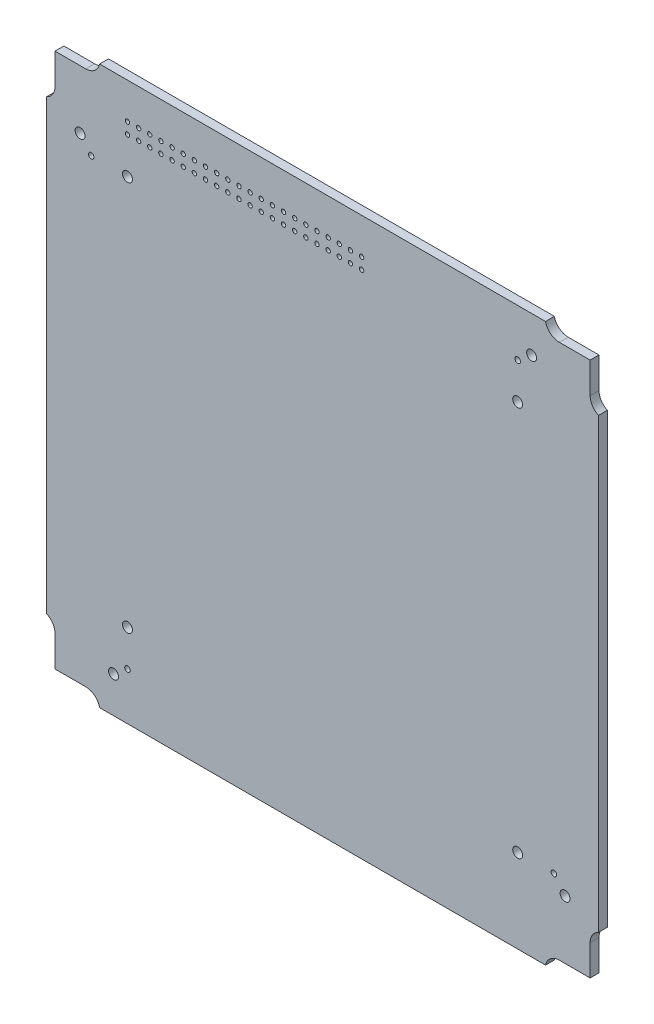
SolidWorks part; units mm, degrees
ref_plane "Front Plane" through (0, 0, 0) normal (0, 0, 1) x (1, 0, 0)
ref_plane "Top Plane" through (0, 0, 0) normal (0, 1, 0) x (1, 0, 0)
ref_plane "Right Plane" through (0, 0, 0) normal (1, 0, 0) x (0, 0, -1)
sketch "Sketch1" plane through (0, 0, 0) normal (0, 0, 1) x (1, 0, 0)
  line L0 (-40, 50) -> (-40, 48)
  line L1 (-50, -50) -> (50, -50)
  line L2 (-50, -50) -> (-50, 50)
  line L3 (-50, 50) -> (50, 50)
  line L4 (50, -50) -> (50, 50)
  line L5 (-50, -50) -> (50, 50) construction
  line L6 (-50, 50) -> (50, -50) construction
  line L7 (-50, 50) -> (-40, 50)
  line L8 (-50, 50) -> (-50, 40)
  line L9 (-40, 48) -> (-48, 48)
  line L10 (-48, 48) -> (-48, 40)
  line L11 (50, 50) -> (40, 50)
  line L12 (50, 50) -> (50, 40)
  line L13 (-48, 40) -> (-50, 40)
  line L14 (50, 40) -> (48, 40)
  line L15 (-50, -50) -> (-37.8649, -50)
  line L16 (-50, -50) -> (-50, -37.8649)
  line L17 (50, 50) -> (50, 40)
  line L18 (50, 50) -> (40, 50)
  line L19 (50, -50) -> (41.5, -50)
  line L20 (50, -50) -> (50, -41.5)
  line L21 (48, 40) -> (48, 48)
  line L22 (48, 48) -> (40, 48)
  line L23 (40, 48) -> (40, 50)
  line L24 (40, -50) -> (40, -48)
  line L25 (50, -50) -> (40, -50)
  line L26 (50, -50) -> (50, -40)
  line L27 (40, -48) -> (48, -48)
  line L28 (48, -48) -> (48, -40)
  line L29 (48, -40) -> (50, -40)
  line L30 (-50, -40) -> (-48, -40)
  line L31 (-50, -50) -> (-50, -40)
  line L32 (-50, -50) -> (-40, -50)
  line L33 (-48, -40) -> (-48, -48)
  line L34 (-48, -48) -> (-40, -48)
  line L35 (-40, -48) -> (-40, -50)
  point P0 (0, 0)
  point P38 (0, 0)
  dimension "D1" = 100
  dimension "D2" = 100
  dimension "D3" = 2
  dimension "D4" = 10
  dimension "D5" = 4
extrude "Boss-Extrude1" add sketch "Sketch1" along normal blind 1.5875 contours L1 L4 L3 L2 region at (0, 0, 0)
fillet "Fillet1" radius 2.54 8 edges at (-48, -40, 0.7937) (-40, -48, 0.7937) (40, -48, 0.7937) (48, -40, 0.7937) (48, 40, 0.7937) (40, 48, 0.7937) (-40, 48, 0.7937) (-48, 40, 0.7937)
sketch "Sketch5" plane through (0, 0, 1.5875) normal (0, 0, 1) x (1, 0, 0)
  line L0 (0, 50) -> (0, -50) construction
  line L5 (-40, 50) -> (40, 50) construction
  line L6 (-40, -50) -> (40, -50) construction
  line L8 (-35.7478, 50) -> (8.2522, 50) construction
  line L9 (-35.7478, 50) -> (-35.7478, 45.8) construction
  line L10 (-35.7478, 45.8) -> (8.2522, 45.8) construction
  line L11 (8.2522, 50) -> (8.2522, 45.8) construction
  circle A0 centre (-35, 43.55) radius 0.395
  circle A1 centre (-33, 43.55) radius 0.395
  circle A2 centre (-31, 43.55) radius 0.395
  circle A3 centre (-29, 43.55) radius 0.395
  circle A4 centre (-27, 43.55) radius 0.395
  circle A5 centre (-25, 43.55) radius 0.395
  circle A6 centre (-23, 43.55) radius 0.395
  circle A7 centre (-21, 43.55) radius 0.395
  circle A8 centre (-19, 43.55) radius 0.395
  circle A9 centre (-17, 43.55) radius 0.395
  circle A10 centre (-15, 43.55) radius 0.395
  circle A11 centre (-13, 43.55) radius 0.395
  circle A12 centre (-11, 43.55) radius 0.395
  circle A13 centre (-9, 43.55) radius 0.395
  circle A14 centre (-7, 43.55) radius 0.395
  circle A15 centre (-5, 43.55) radius 0.395
  circle A16 centre (-3, 43.55) radius 0.395
  circle A17 centre (-1, 43.55) radius 0.395
  circle A18 centre (1, 43.55) radius 0.395
  circle A19 centre (3, 43.55) radius 0.395
  circle A20 centre (5, 43.55) radius 0.395
  circle A21 centre (7, 43.55) radius 0.395
  circle A22 centre (-33, 41.55) radius 0.395
  circle A23 centre (-31, 41.55) radius 0.395
  circle A24 centre (-29, 41.55) radius 0.395
  circle A25 centre (-27, 41.55) radius 0.395
  circle A26 centre (-25, 41.55) radius 0.395
  circle A27 centre (-23, 41.55) radius 0.395
  circle A28 centre (-21, 41.55) radius 0.395
  circle A29 centre (-19, 41.55) radius 0.395
  circle A30 centre (-17, 41.55) radius 0.395
  circle A31 centre (-15, 41.55) radius 0.395
  circle A32 centre (-13, 41.55) radius 0.395
  circle A33 centre (-11, 41.55) radius 0.395
  circle A34 centre (-9, 41.55) radius 0.395
  circle A35 centre (-7, 41.55) radius 0.395
  circle A36 centre (-5, 41.55) radius 0.395
  circle A37 centre (-3, 41.55) radius 0.395
  circle A38 centre (-1, 41.55) radius 0.395
  circle A39 centre (1, 41.55) radius 0.395
  circle A40 centre (3, 41.55) radius 0.395
  circle A41 centre (5, 41.55) radius 0.395
  circle A42 centre (7, 41.55) radius 0.395
  circle A43 centre (-35, 41.55) radius 0.395
  dimension "D5" = 0.79
  dimension "D2" = 2.25
  dimension "D3" = 2
  dimension "D4" = 2
  dimension "D8" = 1
  dimension "D9" = 44
  dimension "D10" = 4.2
  dimension "D6" = 22
  dimension "D7" = 2
extrude "Cut-Extrude1" cut sketch "Sketch5" against normal through all
sketch "Sketch6" plane through (0, 0, 1.5875) normal (0, 0, 1) x (1, 0, 0)
  line L0 (-40, 50) -> (40, 50) construction
  line L1 (-49.5, 50) -> (49.5, 50)
  line L2 (-49.5, 50) -> (-49.5, -50)
  line L3 (-49.5, -50) -> (49.5, -50)
  line L4 (49.5, 50) -> (49.5, -50)
  line L5 (-40, -50) -> (40, -50) construction
  line L6 (50, -40) -> (50, 40) construction
  dimension "D1" = 99
  dimension "D2" = 0.5
extrude "Cut-Extrude2" cut sketch "Sketch6" against normal through all flip side to cut
sketch "Sketch2" plane through (0, 0, 1.5875) normal (0, 0, 1) x (1, 0, 0)
  line L0 (-36.5, 41) -> (36.5, 41)
  line L1 (-39, 38.5) -> (-36.5, 41)
  line L2 (39, 38.5) -> (39, 26.5)
  line L3 (36.5, 24) -> (-36.5, 24)
  line L4 (-39, 26.5) -> (-39, 38.5)
  line L5 (-36.5, 24) -> (-39, 26.5)
  line L6 (0, 0) -> (0, 50) construction
  line L7 (36.5, 41) -> (39, 38.5)
  line L8 (39, 26.5) -> (36.5, 24)
  line L9 (-36.5, 22.75) -> (36.5, 22.75)
  line L10 (-39, 20.25) -> (-36.5, 22.75)
  line L11 (39, 20.25) -> (39, 8.25)
  line L12 (36.5, 5.75) -> (-36.5, 5.75)
  line L13 (-39, 8.25) -> (-39, 20.25)
  line L14 (-36.5, 5.75) -> (-39, 8.25)
  line L15 (36.5, 22.75) -> (39, 20.25)
  line L16 (39, 8.25) -> (36.5, 5.75)
  line L17 (-36.5, 4.5) -> (36.5, 4.5)
  line L18 (-39, 2) -> (-36.5, 4.5)
  line L19 (39, 2) -> (39, -10)
  line L20 (36.5, -12.5) -> (-36.5, -12.5)
  line L21 (-39, -10) -> (-39, 2)
  line L22 (-36.5, -12.5) -> (-39, -10)
  line L23 (36.5, 4.5) -> (39, 2)
  line L24 (39, -10) -> (36.5, -12.5)
  line L25 (-36.5, -13.75) -> (36.5, -13.75)
  line L26 (-39, -16.25) -> (-36.5, -13.75)
  line L27 (39, -16.25) -> (39, -28.25)
  line L28 (36.5, -30.75) -> (-36.5, -30.75)
  line L29 (-39, -28.25) -> (-39, -16.25)
  line L30 (-40, 50) -> (40, 50) construction
  line L33 (-36.5, -30.75) -> (-39, -28.25)
  line L34 (36.5, -13.75) -> (39, -16.25)
  line L36 (39, -28.25) -> (36.5, -30.75)
  line L37 (-36.5, -32) -> (36.5, -32)
  line L38 (-39, -34.5) -> (-36.5, -32)
  line L39 (39, -34.5) -> (39, -46.5)
  line L40 (36.5, -49) -> (-36.5, -49)
  line L41 (-39, -46.5) -> (-39, -34.5)
  line L42 (-36.5, -49) -> (-39, -46.5)
  line L43 (36.5, -32) -> (39, -34.5)
  line L44 (39, -46.5) -> (36.5, -49)
  line L45 (-40, -50) -> (40, -50) construction
  point P0 (-39, 41)
  point P3 (39, 41)
  point P4 (39, 24)
  point P5 (-39, 24)
  point P19 (-39, 22.75)
  point P21 (39, 22.75)
  point P22 (39, 5.75)
  point P23 (-39, 5.75)
  point P31 (-39, 4.5)
  point P33 (39, 4.5)
  point P34 (39, -12.5)
  point P35 (-39, -12.5)
  point P43 (-39, -13.75)
  point P45 (39, -13.75)
  point P46 (39, -30.75)
  point P47 (-39, -30.75)
  point P55 (-39, -32)
  point P57 (39, -32)
  point P58 (39, -49)
  point P59 (-39, -49)
  dimension "D1" = 78
  dimension "D2" = 17
  dimension "D3" = 5
  dimension "D4" = 1
  dimension "D5" = 9
hole_wizard "Ø1.0 (1) Diameter Hole1" positions "Sketch8" profile "Sketch9" hole size "Ø1.0" standard "ISO" end condition through all
sketch "Sketch8" plane through (0, 0, 1.5875) normal (0, 0, 1) x (1, 0, 0)
  line L0 (-49.5, 40.1646) -> (-49.5, -40.1646) construction
  line L2 (-40, 50) -> (40, 50) construction
  point P0 (-41.5, 35)
  dimension "D1" = 8
  dimension "D2" = 15
sketch "Sketch9" plane through (-41.5, 35, 1.5875) normal (1, 0, 0) x (0, -1, 0)
  line L0 (0, 0) -> (0, 1.5875)
  line L1 (0, 1.5875) -> (0.5, 1.5875)
  line L2 (0.5, 1.5875) -> (0.5, 0)
  line L5 (0.5, 0) -> (0, 0)
  line L11 (0, -6.35) -> (0, 107.95) construction
  dimension "Thru Hole Dia." = 1
  dimension "Thru Hole Depth" = 1.5875
hole_wizard "#0 Clearance Hole1" positions "Sketch11" profile "Sketch10" hole size "#0" standard "ANSI Inch" end condition through all
sketch "Sketch11" plane through (0, 0, 1.5875) normal (0, 0, 1) x (1, 0, 0)
  point P0 (-43.5, 37.5)
  point P4 (-35, 35)
sketch "Sketch10" plane through (-43.5, 37.5, 1.5875) normal (1, 0, 0) x (0, -1, 0)
  line L0 (0, 0) -> (0, 1.5875)
  line L1 (0, 1.5875) -> (0.889, 1.5875)
  line L2 (0.889, 1.5875) -> (0.889, 0)
  line L5 (0.889, 0) -> (0, 0)
  line L11 (0, -6.35) -> (0, 107.95) construction
  dimension "Thru Hole Dia." = 1.778
  dimension "Thru Hole Depth" = 1.5875
ref_axis "Axis1" through (0, 0, 0) along (0, 0, 1)
pattern_circular "CirPattern1" count 4 over 360 about axis through (0, 0, 0) along (0, 0, 1) of "Ø1.0 (1) Diameter Hole1", "#0 Clearance Hole1"
